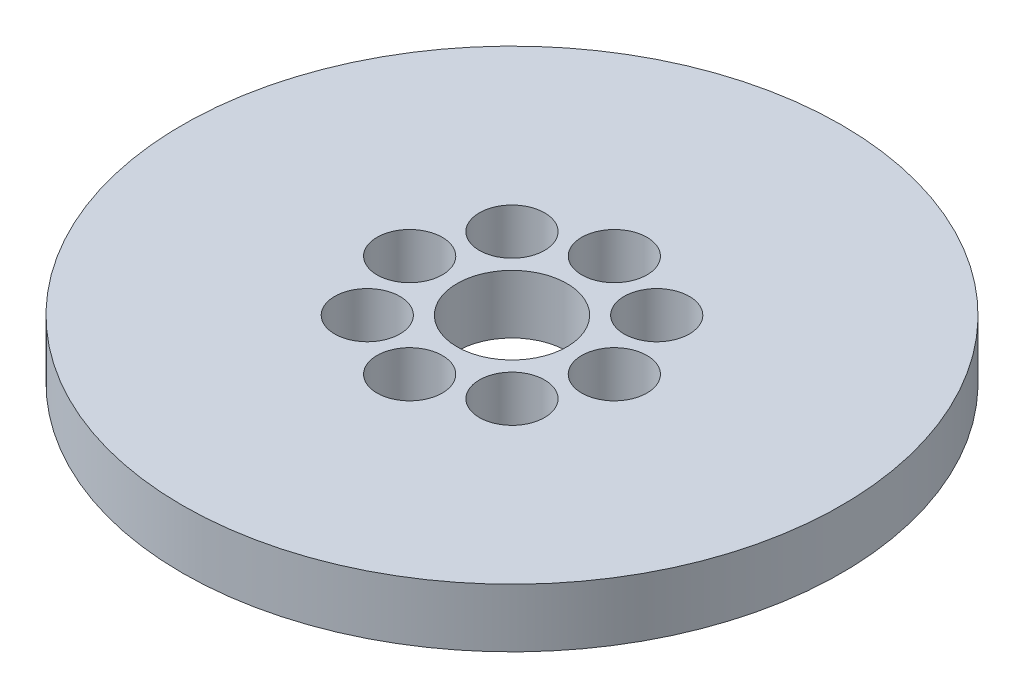
SolidWorks part; units mm, degrees
ref_plane "Front Plane" through (0, 0, 0) normal (0, 0, 1) x (1, 0, 0)
ref_plane "Top Plane" through (0, 0, 0) normal (0, 1, 0) x (1, 0, 0)
ref_plane "Right Plane" through (0, 0, 0) normal (1, 0, 0) x (0, 0, -1)
sketch "Sketch1" plane through (0, 0, 0) normal (0, 1, 0) x (1, 0, 0)
  circle A0 centre (0, 0) radius 45
  dimension "FLANGE_OD" = 90
extrude "Boss-Extrude1" add sketch "Sketch1" along normal blind 8
sketch "Sketch2" plane through (0, 0, 0) normal (0, 1, 0) x (1, 0, 0)
  circle A0 centre (0, 0) radius 7.5
  dimension "BORE_D" = 15
extrude "Cut-Extrude1" cut sketch "Sketch2" along normal through all
sketch "Sketch3" plane through (0, 8, 0) normal (0, 1, 0) x (1, 0, 0)
  circle A0 centre (0, 0) radius 13.9738 construction
  circle A1 centre (-13.9738, 0) radius 4.4545
  dimension "BOLT_D" = 8.9091
  dimension "BOLT_PCD" = 27.9477
extrude "Cut-Extrude2" cut sketch "Sketch3" against normal blind 7.0501
pattern_circular "CirPattern1" count 8 over 360 about axis through (0, 0, 0) along (0, 1, 0) of "Cut-Extrude2"
